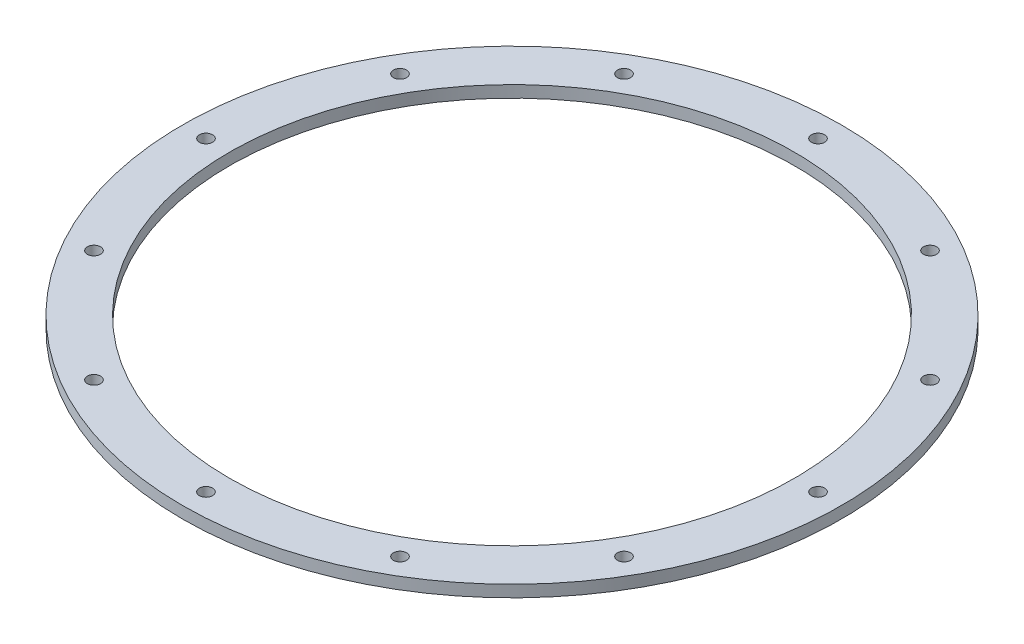
SolidWorks part; units mm, degrees
material "PTFE (general)"
ref_plane "Front Plane" through (0, 0, 0) normal (0, 0, 1) x (1, 0, 0)
ref_plane "Top Plane" through (0, 0, 0) normal (0, 1, 0) x (1, 0, 0)
ref_plane "Right Plane" through (0, 0, 0) normal (1, 0, 0) x (0, 0, -1)
ref_axis "Axis1" through (0, 55, 0) along (0, -1, 0)
sketch "Sketch1" plane through (0, 0, 0) normal (0, 0, 1) x (1, 0, 0)
  line L0 (-38.1, 0) -> (0, 0) construction
  line L1 (-38.1, 0) -> (-44.45, 0)
  line L2 (-38.1, 0) -> (-38.1, 1.5875)
  line L3 (-38.1, 1.5875) -> (-44.45, 1.5875)
  line L4 (-44.45, 0) -> (-44.45, 1.5875)
  line L7 (0, 1.5875) -> (-38.1, 1.5875) construction
  point P12 (-44.45, 0)
  point P18 (-38.1, 1.5875)
revolve "Main" add sketch "Sketch1" angle 360 about axis through (0, 55, 0) along (0, -1, 0)
sketch "Hole Location" plane through (0, 0, 0) normal (0, 1, 0) x (1, 0, 0)
  line L0 (0, 0) -> (-41.275, 0) construction
  circle A0 centre (0, 0) radius 41.275 construction
  dimension "D1" = 82.55
hole_wizard "#50 (0.07) Diameter Hole1" positions "Sketch3" profile "Sketch5" hole size "#50" standard "ANSI Inch" end condition through all
sketch "Sketch3" plane through (0, 0, 0) normal (0, -1, 0) x (-1, 0, 0)
  point P0 (41.275, 0)
sketch "Sketch5" plane through (-41.275, 0, 0) normal (1, 0, 0) x (0, 0, -1)
  line L0 (0, 0) -> (0, 1.5875)
  line L1 (0, 1.5875) -> (0.889, 1.5875)
  line L2 (0.889, 1.5875) -> (0.889, 0)
  line L5 (0.889, 0) -> (0, 0)
  line L11 (0, -6.35) -> (0, 107.95) construction
  dimension "Thru Hole Dia." = 1.778
  dimension "Thru Hole Depth" = 1.5875
pattern_circular "Screw Passthroughs" count 12 over 360 about axis through (0, 55, 0) along (0, -1, 0) of "#50 (0.07) Diameter Hole1"
equation "\"D1@Hole Location\"=\"TANK DIAMETER@Cryo Tank.Assembly\"+\"GASKET SEAT THICKNESS@Cryo Tank.Assembly\""
